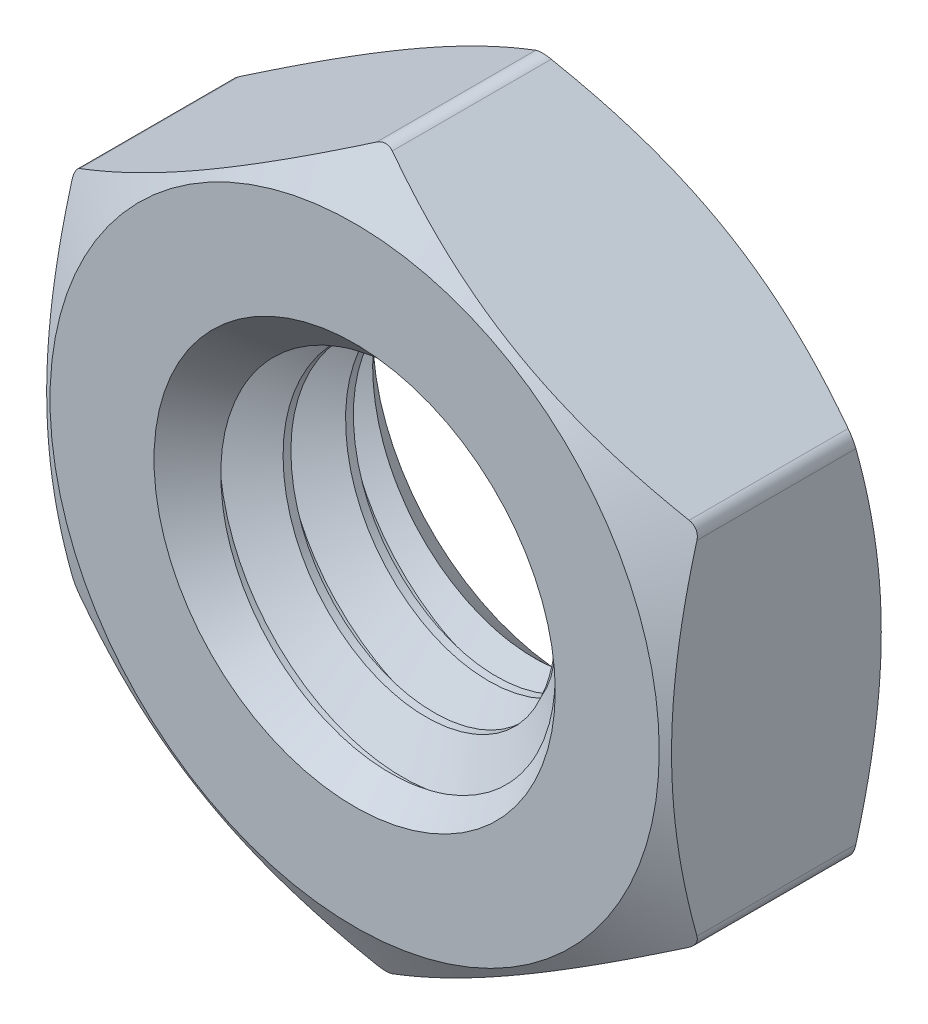
SolidWorks part; units mm, degrees
ref_plane "Front Plane" through (0, 0, 0) normal (0, 0, 1) x (1, 0, 0)
ref_plane "Top Plane" through (0, 0, 0) normal (0, 1, 0) x (1, 0, 0)
ref_plane "Right Plane" through (0, 0, 0) normal (1, 0, 0) x (0, 0, -1)
sketch "Sketch1" plane through (0, 0, 0) normal (1, 0, 0) x (0, 0, -1)
  line L0 (-1.3891, 0) -> (1.3891, 0) construction
  line L1 (-1.3891, -3.9688) -> (-1.3891, 3.9688) construction
  line L2 (1.3891, -3.9688) -> (1.3891, 3.9688) construction
  line L3 (-1.3891, -2.413) -> (-1.3891, 2.413) construction
  line L4 (-2.1332, 2.4989) -> (-1.7363, 1.8115) construction
  line L5 (-1.7363, 1.8115) -> (-1.3395, 2.4989) construction
  line L6 (-1.3395, 2.4989) -> (-2.1332, 2.4989) construction
  line L7 (-2.1084, 2.456) -> (-1.3643, 2.456) construction
  line L8 (-2.0836, 2.413) -> (-1.3891, 2.413) construction
  line L9 (-1.7859, 1.8974) -> (-1.6867, 1.8974) construction
  line L10 (-1.7363, 1.8974) -> (-1.7363, 1.8115) construction
  line L11 (-1.7363, 2.4989) -> (-1.7363, 2.413) construction
  line L12 (-1.3891, 2.5485) -> (-1.2535, 2.413) construction
  point P4 (0, 0)
  point P7 (-1.3891, 0)
  point P11 (1.3891, 0)
  point P14 (-1.3891, 0)
  point P26 (-1.7363, 2.456)
  point P27 (-1.3891, -2.413)
  dimension "Height" = 2.7781
  dimension "Width" = 7.9375
  dimension "Thread Size" = 4.826
  dimension "D1" = 60
  dimension "Thread Pitch" = 0.7937
  dimension "D2" = 0.0992
  dimension "D3" = 45
sketch "Sketch2" plane through (0, 0, 0) normal (0, 0, 1) x (1, 0, 0)
  line L1 (0, 4.5827) -> (-3.9688, 2.2914)
  line L2 (-3.9688, 2.2914) -> (-3.9687, -2.2914)
  line L3 (-3.9687, -2.2914) -> (0, -4.5827)
  line L4 (0, -4.5827) -> (3.9688, -2.2914)
  line L5 (3.9688, -2.2914) -> (3.9688, 2.2914)
  line L6 (3.9688, 2.2914) -> (0, 4.5827)
  circle A0 centre (0, 0) radius 3.9688 construction
  circle A1 centre (0, 0) radius 2.413
extrude "Boss-Extrude1" add sketch "Sketch2" along normal up to vertex (1.3891 mm away) and the other way up to vertex (1.3891 mm away) up to point (0, -3.9688, 1.3891) other way up to point (0, -3.9688, -1.3891)
sketch "Sketch3" plane through (0, 0, 1.3891) normal (0, 0, 1) x (1, 0, 0)
  circle A0 centre (0, 0) radius 3.8695
  dimension "D1" = 7.7391
extrude "Cut-Extrude1" cut sketch "Sketch3" against normal through all draft 60 flip side to cut
fillet "Fillet1" radius 0.1984 6 edges at (3.9688, -2.2914, -0.2059) (0, -4.5827, -0.2059) (-3.9687, -2.2914, -0.2059) (-3.9688, 2.2914, -0.2059) (3.9688, 2.2914, -0.2059) (0, 4.5827, -0.2059)
sketch "Sketch8" plane through (0, 0, 1.3891) normal (0, 0, 1) x (1, 0, 0)
  circle A0 centre (0, 0) radius 2.5485
extrude "Cut-Extrude4" cut sketch "Sketch8" against normal through all draft 45
mirror "Mirror1" about plane through (0, 0, 0) normal (0, 0, 1) of "Cut-Extrude4", "Cut-Extrude1"
sketch "Sketch4" plane through (0, 0, 0) normal (1, 0, 0) x (0, 0, -1)
  line L1 (-2.1084, 2.456) -> (-1.7859, 1.8974)
  line L2 (-1.7859, 1.8974) -> (-1.6867, 1.8974)
  line L3 (-1.6867, 1.8974) -> (-1.3643, 2.456)
  line L4 (-2.1084, 2.456) -> (-1.3643, 2.456) construction
  line L5 (-2.1084, 2.456) -> (-1.3643, 2.456)
sketch "Sketch5" plane through (0, 0, 1.3891) normal (0, 0, 1) x (1, 0, 0)
  circle A0 centre (0, 0) radius 2.413 construction
  circle A1 centre (0, 0) radius 2.413
curve "Helix/Spiral1" pitch 0.7937 height 3.5719 radius 2.413 centre (0, 0, 1.3891) axis (0, 0, -1) start towards (0, 1, 0)
sweep "Sweep1" add profiles "Sketch4" path "Helix/Spiral1"
sketch "Sketch6" plane through (0, 0, 1.3891) normal (0, 0, 1) x (1, 0, 0)
  circle A0 centre (0, 0) radius 2.5485 construction
  circle A1 centre (0, 0) radius 2.5485
extrude "Cut-Extrude2" cut sketch "Sketch6" along normal through all and the other way through all draft 45
sketch "Sketch7" plane through (0, 0, -1.3891) normal (0, 0, -1) x (-1, 0, 0)
  circle A1 centre (0, 0) radius 2.5485
  circle A2 centre (0, 0) radius 2.5485
  dimension "D1" = 0
extrude "Cut-Extrude3" cut sketch "Sketch7" along normal through all and the other way through all draft 44.95
equation "\"D2@Sketch1\"=\"Thread Pitch@Sketch1\"/8"
equation "\"D4@Helix/Spiral1\"=\"Thread Pitch@Sketch1\""
equation "\"D3@Helix/Spiral1\"=\"Height@Sketch1\"+\"Thread Pitch@Sketch1\""
equation "\"D1@Sketch3\"=\"Width@Sketch1\"*.975"
equation "\"D1@Fillet1\"=\"Width@Sketch1\"*.025"
